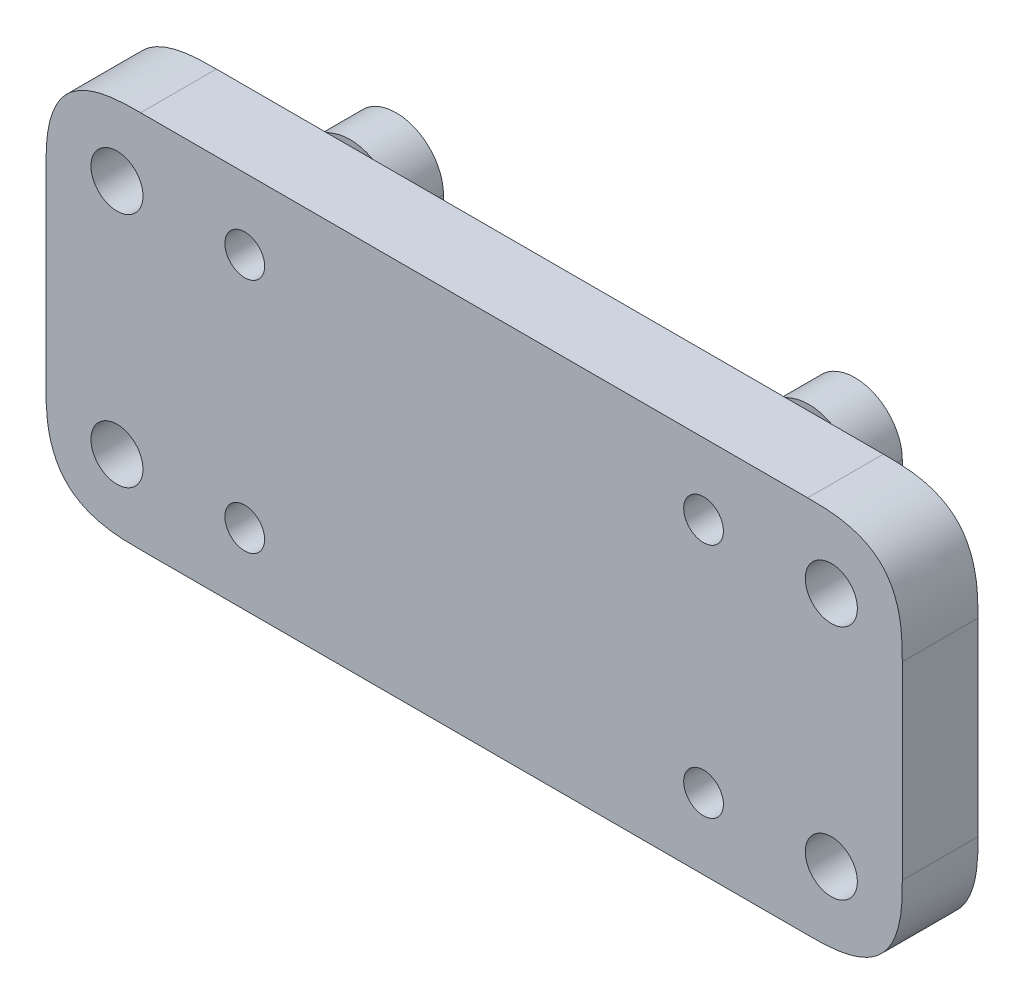
SolidWorks part; units mm, degrees
ref_plane "Front Plane" through (0, 0, 0) normal (0, 0, 1) x (1, 0, 0)
ref_plane "Top Plane" through (0, 0, 0) normal (0, 1, 0) x (1, 0, 0)
ref_plane "Right Plane" through (0, 0, 0) normal (1, 0, 0) x (0, 0, -1)
sketch "Sketch1" plane through (0, 0, 0) normal (0, 0, 1) x (1, 0, 0)
  circle A0 centre (12.75, 8.94) radius 2.5
  circle A1 centre (12.75, -8.94) radius 2.5
  circle A2 centre (-12.75, -8.94) radius 2.5
  circle A3 centre (-12.75, 8.94) radius 2.5
  dimension "D1" = 5
extrude "Boss-Extrude1" add sketch "Sketch1" along normal blind 4
sketch "Sketch2" plane through (0, 0, 4) normal (0, 0, 1) x (1, 0, 0)
  line L1 (45.24, 20) -> (-45.24, 20)
  line L2 (45.24, 20) -> (45.24, -20)
  line L3 (45.24, -20) -> (-45.24, -20)
  line L4 (-45.24, 20) -> (-45.24, -20)
  line L5 (0, 11.43) -> (0, 20) construction
  line L6 (-15.24, 11.43) -> (15.24, 11.43) construction
  line L7 (0, -11.43) -> (0, -20) construction
  line L8 (15.24, -11.43) -> (-15.24, -11.43) construction
  line L9 (15.24, 11.43) -> (15.24, -11.43) construction
  line L10 (-15.24, -11.43) -> (-15.24, 11.43) construction
  dimension "D1" = 30
  dimension "D2" = 40
  dimension "D3" = 30
extrude "Boss-Extrude2" add sketch "Sketch2" along normal blind 8
sketch "Sketch5" plane through (0, 0, 4) normal (0, 0, -1) x (-1, 0, 0)
  line L0 (-37.74, -20) -> (-37.74, -12.5) construction
  line L1 (45.24, -20) -> (-45.24, -20) construction
  line L2 (-37.74, -12.5) -> (-37.74, 12.5) construction
  line L3 (-37.74, 12.5) -> (-37.74, 20) construction
  line L4 (-45.24, 20) -> (45.24, 20) construction
  line L5 (-37.74, -12.5) -> (-45.24, -12.5) construction
  line L6 (-45.24, -20) -> (-45.24, 20) construction
  line L8 (37.74, -20) -> (37.74, -12.5) construction
  line L9 (37.74, -12.5) -> (45.24, -12.5) construction
  line L10 (45.24, 20) -> (45.24, -20) construction
  line L14 (37.74, -12.5) -> (37.74, 12.5) construction
  line L15 (37.74, 12.5) -> (37.74, 20) construction
  point P2 (-37.74, -12.5)
  point P6 (-37.74, 12.5)
  point P16 (-37.74, 12.5)
  point P18 (-37.74, -12.5)
  point P30 (37.74, -12.5)
  point P40 (37.74, 12.5)
  point P49 (37.74, -12.5)
  point P51 (37.74, 12.5)
  dimension "D1" = 25
hole_wizard "CBORE for M5 Hex Head Cap Screw1" positions "Sketch5" profile "Sketch6" counterbore size "M5" standard "ANSI Metric" end condition through all
sketch "Sketch6" plane through (-37.74, 12.5, 4) normal (1, 0, 0) x (0, 1, 0)
  line L0 (0, 0) -> (0, 8)
  line L1 (0, 8) -> (2.75, 8)
  line L3 (2.75, 8) -> (2.75, 3.65)
  line L4 (2.75, 3.65) -> (6.12, 3.65)
  line L5 (6.12, 3.65) -> (6.12, 0)
  line L7 (6.12, 0) -> (0, 0)
  line L11 (0, -6.35) -> (0, 107.95) construction
  dimension "Thru Hole Dia." = 5.5
  dimension "Thru Hole Depth" = 8
  dimension "C'Bore Dia." = 12.24
  dimension "C'Bore Depth" = 3.65
sketch "Sketch9" plane through (0, 0, 0) normal (0, 0, -1) x (-1, 0, 0)
  point P0 (-12.75, -8.94)
  point P3 (-12.75, 8.94)
  point P6 (12.75, -8.94)
  point P9 (12.75, 8.94)
hole_wizard "1/16 (0.0625) Diameter Hole1" positions "Sketch9" profile "Sketch8" hole size "1/16" standard "ANSI Inch"
sketch "Sketch8" plane through (12.75, -8.94, 0) normal (1, 0, 0) x (0, 1, 0)
  line L0 (0, 0) -> (0, 7.4769)
  line L1 (0, 7.4769) -> (0.7937, 7)
  line L2 (0.7937, 7) -> (0.7937, 0)
  line L5 (0.7937, 0) -> (0, 0)
  line L10 (0, 7.4769) -> (-0.7938, 7) construction
  line L11 (0, -6.35) -> (0, 107.95) construction
  dimension "Hole Dia." = 1.5875
  dimension "Hole Depth" = 7
  dimension "Drill Angle" = 118
fillet "Fillet1" radius 10 4 edges at (-45.24, -20, 8) (-45.24, 20, 8) (45.24, 20, 8) (45.24, -20, 8) curvature continuous yes
sketch "Sketch13" plane through (0, 0, 4) normal (0, 0, -1) x (-1, 0, 0)
  line L0 (-24.24, 12.5) -> (-24.24, -12.5) construction
  line L1 (-19.24, 12.5) -> (-19.24, -12.5)
  line L2 (-29.24, 12.5) -> (-29.24, -12.5)
  line L3 (-24.24, 12.5) -> (-24.24, 20) construction
  line L4 (-35.24, 20) -> (35.24, 20) construction
  line L5 (-24.24, -12.5) -> (-24.24, -20) construction
  line L6 (35.24, -20) -> (-35.24, -20) construction
  line L7 (-15.24, 11.43) -> (-15.24, -11.43) construction
  arc A0 (-19.24, 12.5) -> (-29.24, 12.5) centre (-24.24, 12.5) ccw
  arc A1 (-29.24, -12.5) -> (-19.24, -12.5) centre (-24.24, -12.5) ccw
  point P2 (-24.24, 0)
  dimension "D1" = 25
  dimension "D2" = 9
  dimension "D3" = 10
extrude "Boss-Extrude3" add sketch "Sketch13" along normal blind 8
sketch "Sketch16" plane through (0, 0, -4) normal (0, 0, -1) x (-1, 0, 0)
  point P0 (-24.24, -12.5)
  point P3 (-24.24, 12.5)
hole_wizard "M5x0.8 Tapped Hole2" positions "Sketch16" profile "Sketch17" tap size "M5x0.8" standard "ANSI Metric" end condition through all
cosmetic thread "Hole Thread3" parameters "D2"=5
cosmetic thread "Hole Thread4" parameters "D2"=5
sketch "Sketch17" plane through (24.24, -12.5, -4) normal (1, 0, 0) x (0, 1, 0)
  line L0 (0, 0) -> (0, 16.05)
  line L1 (0, 16.05) -> (2.1, 16.05)
  line L2 (2.1, 16.05) -> (2.1, 0)
  line L5 (2.1, 0) -> (0, 0)
  line L11 (0, -6.35) -> (0, 107.95) construction
  dimension "Thru Tap Drill Dia." = 4.2
  dimension "Thru Tap Drill Depth" = 16.05
mirror "Mirror2" about plane through (0, 0, 0) normal (1, 0, 0) of "Boss-Extrude3", "M5x0.8 Tapped Hole2"
cosmetic thread "Hole Thread5" parameters "D2"=5
cosmetic thread "Hole Thread6" parameters "D2"=5
chamfer "Chamfer1" distance 1.8 angle 60 12 edges at (29.24, 0, 4) (24.24, -17.5, 4) (24.24, 17.5, 4) (19.24, 0, 4) (-10.25, 8.94, 4) (-10.25, -8.94, 4) (15.25, 8.94, 4) (15.25, -8.94, 4) (-19.24, 0, 4) (-24.24, 17.5, 4) (-24.24, -17.5, 4) (-29.24, 0, 4) first distance on face at (-24.24, 0, 4)
